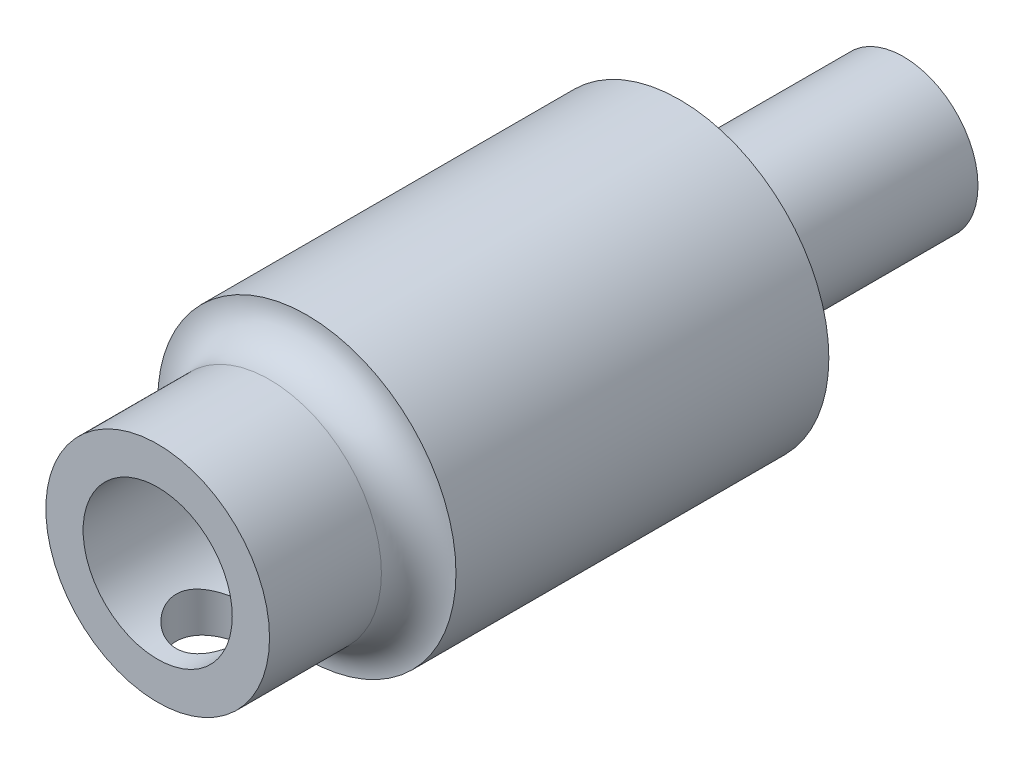
SolidWorks part; units mm, degrees
ref_plane "Plan de face" through (0, 0, 0) normal (0, 0, 1) x (1, 0, 0)
ref_plane "Plan de dessus" through (0, 0, 0) normal (0, 1, 0) x (1, 0, 0)
ref_plane "Plan de droite" through (0, 0, 0) normal (1, 0, 0) x (0, 0, -1)
sketch "Esquisse1" plane through (0, 0, 0) normal (0, 0, 1) x (1, 0, 0)
  circle A0 centre (0, 0) radius 2
  dimension "D1" = 4
extrude "Boss.-Extru.1" add sketch "Esquisse1" along normal blind 5
sketch "Esquisse2" plane through (0, 0, 5) normal (0, 0, 1) x (1, 0, 0)
  circle A0 centre (0, 0) radius 1
  circle A1 centre (0, 0) radius 1.5
  dimension "D1" = 2
  dimension "D2" = 3
extrude "Boss.-Extru.2" add sketch "Esquisse2" along normal blind 2
sketch "Esquisse3" plane through (0, 0, 0) normal (0, 0, -1) x (-1, 0, 0)
  circle A0 centre (0, 0) radius 0.5
  circle A1 centre (0, 0) radius 1
  dimension "D1" = 1
  dimension "D2" = 2
extrude "Boss.-Extru.3" add sketch "Esquisse3" along normal blind 3
fillet "Congé1" radius 0.5 1 edges at (1, 0, 0) type face fillet first side face at (1, 0, 0) second side face at (-1, 0, -3)
fillet "Congé2" radius 0.5 1 edges at (1.5, 0, 5) type face fillet first side face at (1.5, 0, 5) second side face at (1.5, 0, 7)
sketch "Esquisse5" plane through (0, 0, 0) normal (0, 1, 0) x (1, 0, 0)
  line L0 (-1, 1.75) -> (1, 1.75) construction
  line L1 (-1, 3) -> (-1, 0.5) construction
  line L2 (1, 0.5) -> (1, 3) construction
  line L3 (-1.5, -6.25) -> (1.5, -6.25) construction
  line L4 (-1.5, -5.5) -> (-1.5, -7) construction
  line L5 (1.5, -7) -> (1.5, -5.5) construction
  circle A0 centre (0, 1.75) radius 0.5
  circle A1 centre (0, -6.25) radius 0.5
  dimension "D1" = 1
  dimension "D2" = 1
extrude "Enlèv. mat.-Extru.1" cut sketch "Esquisse5" against normal blind 2 contours A1 | A0
